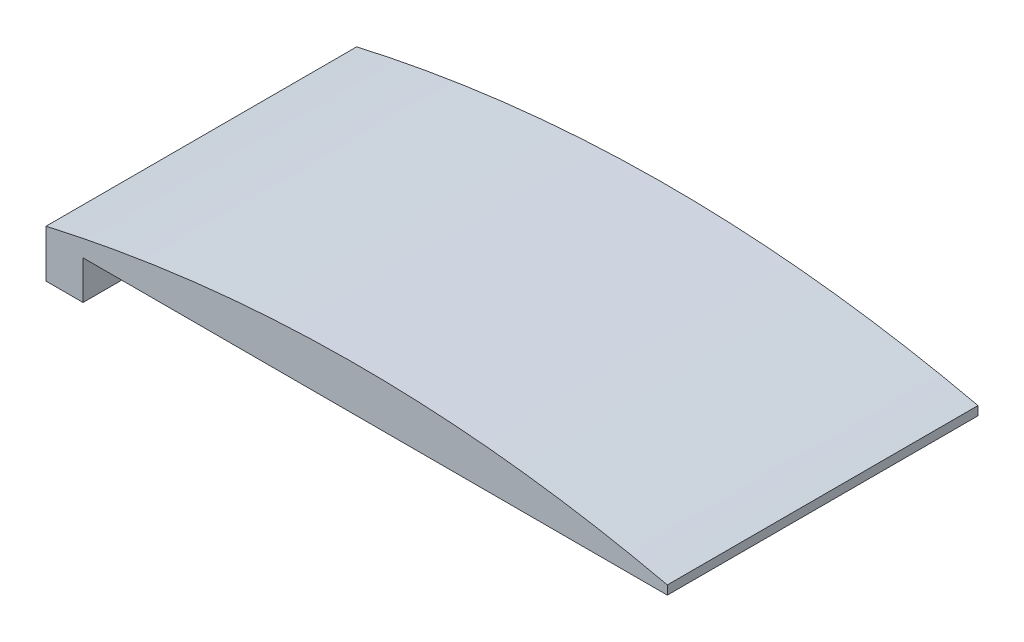
SolidWorks part; units mm, degrees
ref_plane "Front Plane" through (0, 0, 0) normal (0, 0, 1) x (1, 0, 0)
ref_plane "Top Plane" through (0, 0, 0) normal (0, 1, 0) x (1, 0, 0)
ref_plane "Right Plane" through (0, 0, 0) normal (1, 0, 0) x (0, 0, -1)
sketch "Sketch2" plane through (0, 0, 0) normal (0, 1, 0) x (1, 0, 0)
  line L1 (0, 0) -> (140, 0)
  line L2 (0, 0) -> (0, 70)
  line L3 (0, 70) -> (140, 70)
  line L4 (140, 0) -> (140, 70)
  dimension "D1" = 70
  dimension "D2" = 140
extrude "Boss-Extrude1" add sketch "Sketch2" along normal blind 10
sketch "Sketch3" plane through (0, 0, 0) normal (0, 0, 1) x (1, 0, 0)
  line L0 (0, 0) -> (140, 0)
  line L1 (0, 10) -> (0, 0) construction
  line L2 (140, 10) -> (140, 0) construction
  line L3 (0, 2) -> (0, 0)
  line L4 (140, 2) -> (140, 0)
  line L5 (0, 10) -> (140, 10) construction
  spline S0 degree 2 poles (0, 2) (70, 18) (140, 2) knots 0 0 0 1 1 1
  point P2 (70, 5.7845)
  point P5 (0, 2)
  dimension "D1" = 2
extrude "Boss-Extrude2" add sketch "Sketch3" against normal blind 70 separate body
combine bodies "Combine1" operation type common bodies to combine 103 101
sketch "Sketch4" plane through (0, 0, 0) normal (0, 0, 1) x (1, 0, 0)
  line L1 (0, 1.2832) -> (8.35, 1.2832)
  line L2 (0, 1.2832) -> (0, -8.7168)
  line L3 (0, -8.7168) -> (8.35, -8.7168)
  line L4 (8.35, 1.2832) -> (8.35, -8.7168)
  dimension "D1" = 8.35
  dimension "D2" = 0
  dimension "D3" = 1.2832
  dimension "D4" = 10
extrude "Boss-Extrude3" add sketch "Sketch4" against normal blind 5
sketch "Sketch5" plane through (0, 0, -5) normal (0, 0, -1) x (-1, 0, 0)
  line L0 (0, 0) -> (0, -8.7168) construction
  line L1 (-8.35, -8.7168) -> (0, -8.7168)
  line L2 (-8.35, -8.7168) -> (-8.35, -2.8668)
  line L3 (-8.35, -2.8668) -> (0, -2.8668)
  line L4 (0, -8.7168) -> (0, -2.8668)
  dimension "D1" = 5.85
extrude "Boss-Extrude4" add sketch "Sketch5" along normal blind 65
